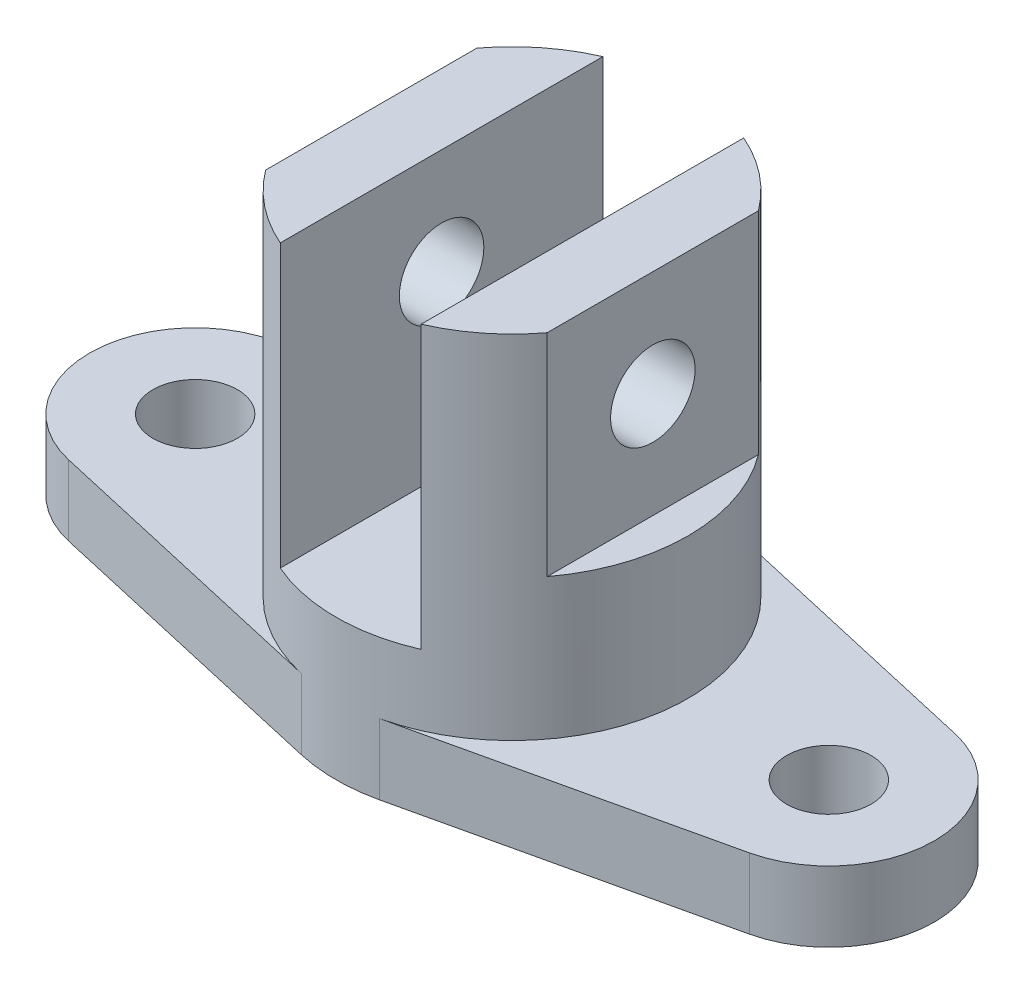
SolidWorks part; units mm, degrees
ref_plane "Alzado" through (0, 0, 0) normal (0, 0, 1) x (1, 0, 0)
ref_plane "Planta" through (0, 0, 0) normal (0, 1, 0) x (1, 0, 0)
ref_plane "Vista lateral" through (0, 0, 0) normal (1, 0, 0) x (0, 0, -1)
sketch "Croquis1" plane through (0, 0, 0) normal (0, 1, 0) x (1, 0, 0)
  line L0 (0, 0) -> (-45, 0) construction
  line L2 (-48.3333, 14.6249) -> (-5.5556, 24.3749)
  line L3 (-48.3333, -14.6249) -> (-5.5556, -24.3749)
  line L4 (0, 0) -> (0, 25) construction
  line L5 (48.3333, -14.6249) -> (5.5556, -24.3749)
  line L6 (48.3333, 14.6249) -> (5.5556, 24.3749)
  circle A0 centre (0, 0) radius 25
  circle A1 centre (-45, 0) radius 6
  arc A3 (-48.3333, -14.6249) -> (-48.3333, 14.6249) centre (-45, 0) cw
  circle A4 centre (45, 0) radius 6
  arc A5 (48.3333, -14.6249) -> (48.3333, 14.6249) centre (45, 0) ccw
  point P18 (0, 0)
  point P19 (0, 0)
  point P20 (43.7445, 0)
  dimension "D1" = 50
  dimension "D2" = 12
  dimension "D3" = 15
  dimension "D4" = 45
extrude "Saliente-Extruir1" add sketch "Croquis1" along normal blind 10 contours L5 A5 L6 A0 A4 | A3 L3 A0 L2 A1 region at (-36.9479, 0, 0) region at (36.9479, 0, 0)
extrude "Saliente-Extruir2" add sketch "Croquis1<4>" along normal blind 60 contours A0 region at (0, 0, 0)
sketch "Croquis1<4>" plane through (0, 0, 0) normal (0, 1, 0) x (1, 0, 0) same geometry as "Croquis1"
sketch "Croquis2" plane through (0, 60, 0) normal (0, 1, 0) x (1, 0, 0)
  line L1 (-10, -28.3163) -> (10, -28.3163)
  line L2 (-10, -28.3163) -> (-10, 28.3163)
  line L3 (-10, 28.3163) -> (10, 28.3163)
  line L4 (10, -28.3163) -> (10, 28.3163)
  line L5 (-10, -28.3163) -> (10, 28.3163) construction
  line L6 (-10, 28.3163) -> (10, -28.3163) construction
  point P0 (0, 0)
  dimension "D1" = 20
extrude "Cortar-Extruir2" cut sketch "Croquis2" against normal blind 40
sketch "Croquis3" plane through (0, 60, 0) normal (0, 1, 0) x (1, 0, 0)
  line L0 (0, 0) -> (0, 25) construction
  line L1 (-20, 25) -> (-25, 25)
  line L2 (-20, 25) -> (-20, -25)
  line L3 (-20, -25) -> (-25, -25)
  line L4 (-25, 25) -> (-25, -25)
  line L5 (20, -25) -> (25, -25)
  line L6 (25, 25) -> (25, -25)
  line L7 (20, 25) -> (25, 25)
  line L8 (20, 25) -> (20, -25)
  arc A0 (10, 22.9129) -> (-10, 22.9129) centre (0, 0) ccw construction
  arc A1 (-10, -22.9129) -> (10, -22.9129) centre (0, 0) ccw construction
  arc A2 (-10, 22.9129) -> (-10, -22.9129) centre (0, 0) ccw construction
  dimension "D1" = 40
extrude "Cortar-Extruir3" cut sketch "Croquis3" against normal blind 30
sketch "Croquis5" plane through (20, 0, 0) normal (1, 0, 0) x (0, 0, -1)
  line L0 (0, 30) -> (0, 60) construction
  line L1 (15, 30) -> (-15, 30) construction
  line L2 (15, 60) -> (-15, 60) construction
  line L3 (-15, 45) -> (15, 45) construction
  line L4 (-15, 30) -> (-15, 60) construction
  line L5 (15, 60) -> (15, 30) construction
  circle A0 centre (0, 45) radius 6
  point P2 (0, 45)
  point P9 (-4.8149, 39.3395)
  dimension "D1" = 12
extrude "Cortar-Extruir4" cut sketch "Croquis5" against normal through all both and the other way through all
